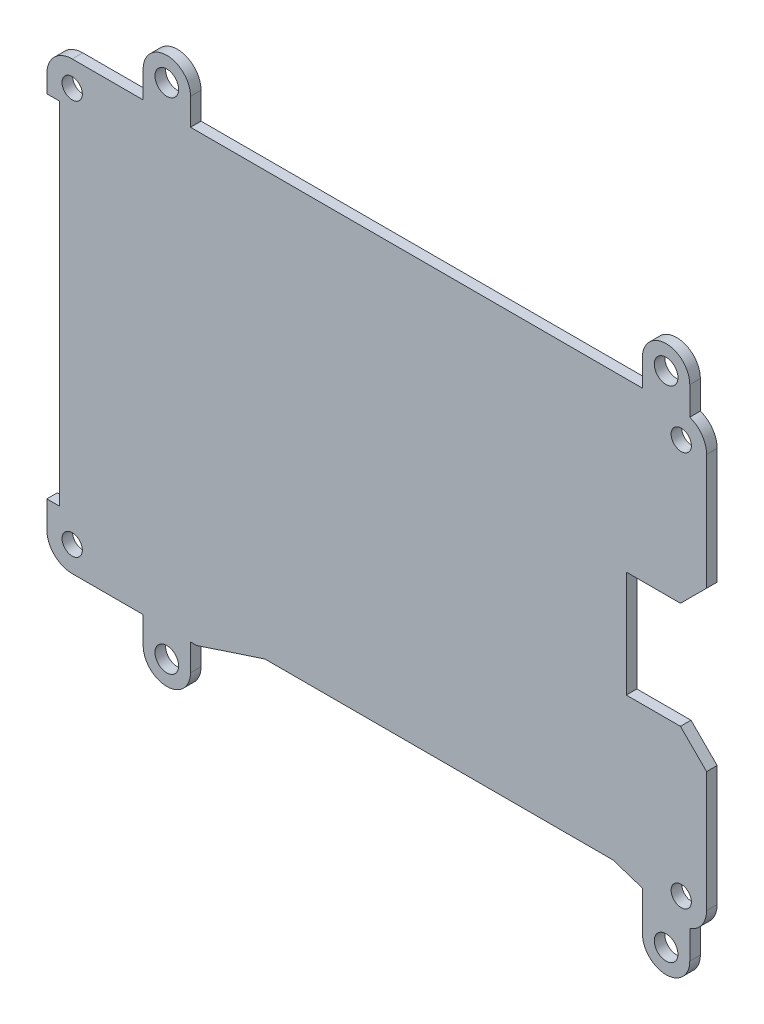
SolidWorks part; units mm, degrees
ref_plane "Front Plane" through (0, 0, 0) normal (0, 0, 1) x (1, 0, 0)
ref_plane "Top Plane" through (0, 0, 0) normal (0, 1, 0) x (1, 0, 0)
ref_plane "Right Plane" through (0, 0, 0) normal (1, 0, 0) x (0, 0, -1)
sketch "Sketch1" plane through (0, 0, 0) normal (0, 0, 1) x (1, 0, 0)
  line L0 (-301.9473, 111.7465) -> (-305.8779, 115.6771) construction
  line L1 (-305.8779, 115.6771) -> (-316.1078, 115.6771) construction
  line L2 (-316.1078, 115.6771) -> (-316.1078, 128.8851) construction
  line L3 (-316.1078, 128.8851) -> (-305.8779, 128.8851) construction
  line L4 (-305.8779, 128.8851) -> (-301.9473, 132.8157) construction
  line L5 (-301.9473, 132.8157) -> (-301.9473, 150.9704) construction
  line L6 (-305.7573, 154.7804) -> (-397.2471, 154.7804) construction
  line L7 (-401.0571, 150.9566) -> (-401.0571, 148.341) construction
  line L8 (-401.0571, 148.341) -> (-399.1521, 148.341) construction
  line L9 (-399.1521, 148.341) -> (-399.1521, 95.6449) construction
  line L10 (-399.1521, 95.6449) -> (-401.0571, 95.6449) construction
  line L11 (-401.0571, 95.6449) -> (-401.0571, 91.6593) construction
  line L12 (-397.2472, 87.8217) -> (-378.5565, 87.8217) construction
  line L13 (-378.5565, 87.8217) -> (-368.3165, 91.1883) construction
  line L14 (-368.3165, 91.1883) -> (-315.9973, 91.1883) construction
  line L15 (-315.9973, 91.1883) -> (-305.7573, 87.8217) construction
  line L16 (-301.9473, 91.6317) -> (-301.9473, 111.7465) construction
  line L17 (-301.9473, 111.7465) -> (-305.8779, 115.6771)
  line L18 (-305.8779, 115.6771) -> (-316.1078, 115.6771)
  line L19 (-316.1078, 115.6771) -> (-316.1078, 128.8851)
  line L20 (-316.1078, 128.8851) -> (-305.8779, 128.8851)
  line L21 (-305.8779, 128.8851) -> (-301.9473, 132.8157)
  line L22 (-301.9473, 132.8157) -> (-301.9473, 150.9704)
  line L23 (-305.7573, 154.7804) -> (-397.2471, 154.7804)
  line L24 (-401.0571, 150.9566) -> (-401.0571, 148.341)
  line L25 (-401.0571, 148.341) -> (-399.1521, 148.341)
  line L26 (-399.1521, 148.341) -> (-399.1521, 95.6449)
  line L27 (-399.1521, 95.6449) -> (-401.0571, 95.6449)
  line L28 (-401.0571, 95.6449) -> (-401.0571, 91.6593)
  line L29 (-397.2472, 87.8217) -> (-378.5565, 87.8217)
  line L30 (-378.5565, 87.8217) -> (-368.3165, 91.1883)
  line L31 (-368.3165, 91.1883) -> (-315.9973, 91.1883)
  line L32 (-315.9973, 91.1883) -> (-305.7573, 87.8217)
  line L33 (-301.9473, 91.6317) -> (-301.9473, 111.7465)
  circle A0 centre (-305.7573, 91.6317) radius 1.3559 construction
  circle A1 centre (-305.7573, 150.9704) radius 1.3559 construction
  circle A2 centre (-397.2471, 150.9704) radius 1.3559 construction
  circle A3 centre (-397.2472, 91.6317) radius 1.3559 construction
  circle A4 centre (-305.7573, 91.6317) radius 1.3559
  circle A5 centre (-305.7573, 150.9704) radius 1.3559
  circle A6 centre (-397.2471, 150.9704) radius 1.3559
  circle A7 centre (-397.2472, 91.6317) radius 1.3559
  arc A8 (-301.9473, 150.9704) -> (-305.7573, 154.7804) centre (-305.7573, 150.9704) ccw construction
  arc A9 (-397.2471, 154.7804) -> (-401.0571, 150.9566) centre (-397.2471, 150.9704) ccw construction
  arc A10 (-401.0571, 91.6593) -> (-397.2472, 87.8217) centre (-397.2472, 91.6317) ccw construction
  arc A11 (-305.7573, 87.8217) -> (-301.9473, 91.6317) centre (-305.7573, 91.6317) ccw construction
  arc A12 (-301.9473, 150.9704) -> (-305.7573, 154.7804) centre (-305.7573, 150.9704) ccw
  arc A13 (-397.2471, 154.7804) -> (-401.0571, 150.9566) centre (-397.2471, 150.9704) ccw
  arc A14 (-401.0571, 91.6593) -> (-397.2472, 87.8217) centre (-397.2472, 91.6317) ccw
  arc A15 (-305.7573, 87.8217) -> (-301.9473, 91.6317) centre (-305.7573, 91.6317) ccw
extrude "Boss-Extrude1" add sketch "Sketch1" along normal blind 1.5875
sketch "Sketch2" plane through (0, 0, 1.5875) normal (0, 0, 1) x (1, 0, 0)
  line L0 (-351.5022, 121.301) -> (-351.5022, 159.401) construction
  line L1 (-301.9473, 150.9704) -> (-301.9473, 91.6317) construction
  line L2 (-401.0571, 121.301) -> (-301.9473, 121.301) construction
  line L3 (-351.5022, 83.201) -> (-351.5022, 159.401) construction
  line L4 (-361.0272, 83.201) -> (-361.0272, 159.401)
  line L5 (-341.9772, 83.201) -> (-341.9772, 159.401)
  line L6 (-361.0272, 154.7804) -> (-341.9772, 154.7804)
  line L7 (-305.7573, 154.7804) -> (-397.2471, 154.7804) construction
  line L8 (-361.0272, 91.6317) -> (-341.9772, 91.6317)
  circle A0 centre (-351.5022, 159.401) radius 3.175
  arc A1 (-361.0272, 83.201) -> (-341.9772, 83.201) centre (-351.5022, 83.201) ccw
  arc A2 (-341.9772, 159.401) -> (-361.0272, 159.401) centre (-351.5022, 159.401) ccw
  circle A3 centre (-351.5022, 83.201) radius 3.175
  point P13 (-351.5022, 121.301)
  line M11 (-305.7573, 154.7804) -> (-397.2471, 154.7804)
  line M21 (-368.3165, 91.1883) -> (-315.9973, 91.1883)
  dimension "D1" = 6.35
  dimension "D2" = 38.1
  dimension "D3" = 19.05
extrude "Boss-Extrude2" [suppressed] add sketch "Sketch2" against normal blind 1.5875 contours L5 A2 L4 A0 M11 | L4 A1 L5 A3 M21
sketch "Sketch3" plane through (0, 0, 1.5875) normal (0, 0, 1) x (1, 0, 0)
  circle A0 centre (-397.2471, 150.9704) radius 1.524
  circle A1 centre (-305.7573, 150.9704) radius 1.524
  circle A2 centre (-305.7573, 91.6317) radius 1.524
  circle A3 centre (-397.2472, 91.6317) radius 1.524
  dimension "D1" = 3.048
extrude "Cut-Extrude1" cut sketch "Sketch3" against normal through all
sketch "Sketch4" plane through (0, 0, 1.5875) normal (0, 0, 1) x (1, 0, 0)
  line L0 (-301.9473, 133.571) -> (-305.8779, 129.6471)
  line L2 (-301.9473, 132.8157) -> (-301.9473, 150.9704) construction
  line L3 (-305.8779, 129.6471) -> (-314.0123, 129.6471)
  line L4 (-314.0123, 129.6471) -> (-314.0123, 113.6451)
  line L5 (-314.0123, 113.6451) -> (-305.8779, 113.6451)
  line L7 (-305.8779, 113.6451) -> (-301.9473, 109.7145)
  line L11 (-301.9473, 91.6317) -> (-301.9473, 111.7465) construction
  line L12 (-301.9473, 109.7145) -> (-301.9473, 133.571)
  dimension "D1" = 18.0828
  dimension "D2" = 16.002
  dimension "D3" = 8.1344
  dimension "D4" = 3.9306
  dimension "D5" = 23.8566
  dimension "D6" = 8.1344
  dimension "D7" = 5.5588
sketch "Sketch5" plane through (0, 0, 1.5875) normal (0, 0, 1) x (1, 0, 0)
  line L0 (-316.1078, 128.8851) -> (-305.8779, 128.8851) construction
  line L1 (-314.0123, 128.8851) -> (-316.1078, 128.8851)
  line L2 (-314.0123, 128.8851) -> (-314.0123, 115.6771)
  line L3 (-314.0123, 115.6771) -> (-316.1078, 115.6771)
  line L4 (-316.1078, 128.8851) -> (-316.1078, 115.6771)
  line L5 (-301.9473, 91.6317) -> (-301.9473, 111.7465) construction
  dimension "D1" = 12.065
extrude "Boss-Extrude3" add sketch "Sketch5" against normal up to vertex (1.5875 mm away) up to point (-316.1078, 128.8851, 0)
extrude "Cut-Extrude2" cut sketch "Sketch4" against normal through all
sketch "Sketch6" [suppressed] plane through (0, 0, 0) normal (0, 0, -1) x (-1, 0, 0)
  line L0 (351.5022, 154.7804) -> (351.5022, 91.1883) construction
  line L1 (368.3165, 91.1883) -> (315.9973, 91.1883) construction
  line L5 (305.7573, 154.7804) -> (397.2471, 154.7804) construction
  line L6 (379.7343, 158.5904) -> (379.7343, 154.7804)
  line L7 (379.7343, 154.7804) -> (386.7701, 154.7804)
  line L8 (386.7701, 154.7804) -> (386.7701, 158.5904)
  line L9 (347.9843, 87.3783) -> (347.9843, 91.1883)
  line L10 (347.9843, 91.1883) -> (355.0201, 91.1883)
  line L11 (355.0201, 91.1883) -> (355.0201, 87.3783)
  line L13 (316.2343, 154.7804) -> (316.2343, 158.5904)
  line L14 (323.2701, 154.7804) -> (316.2343, 154.7804)
  line L15 (323.2701, 158.5904) -> (323.2701, 154.7804)
  circle A0 centre (351.5022, 87.3783) radius 1.778
  circle A1 centre (351.5022, 87.3783) radius 3.5179
  circle A2 centre (383.2522, 158.5904) radius 3.5179
  circle A3 centre (383.2522, 158.5904) radius 1.778
  circle A4 centre (319.7522, 158.5904) radius 1.778
  circle A5 centre (319.7522, 158.5904) radius 3.5179
  dimension "D1" = 7.0358
  dimension "D2" = 7.0358
  dimension "D6" = 3.556
  dimension "D3" = 3.81
  dimension "D4" = 63.5
  dimension "D5" = 3.81
extrude "Boss-Extrude4" [suppressed] add sketch "Sketch6" against normal up to vertex up to point (-397.2472, 87.8217, 1.5875)
sketch "Sketch7" plane through (0, 0, 0) normal (0, 0, -1) x (-1, 0, 0)
  line L0 (397.2471, 154.7804) -> (397.2472, 87.8217) construction
  line L1 (308.0318, 158.801) -> (383.0318, 158.8011) construction
  line L2 (308.0318, 158.801) -> (308.0318, 83.801) construction
  line L3 (308.0318, 83.801) -> (383.0318, 83.801) construction
  line L4 (383.0318, 158.8011) -> (383.0318, 83.801) construction
  line L6 (397.2472, 121.301) -> (383.0318, 121.301) construction
  line L8 (304.4758, 158.801) -> (304.4758, 154.5584)
  line L9 (311.5878, 158.801) -> (311.5878, 154.7804)
  line L10 (305.7573, 154.7804) -> (397.2471, 154.7804) construction
  line L11 (379.4758, 158.8011) -> (379.4758, 154.7804)
  line L12 (386.5878, 158.8011) -> (386.5878, 154.7804)
  line L13 (386.5878, 154.7804) -> (379.4758, 154.7804)
  line L14 (379.4758, 83.801) -> (379.4758, 87.8217)
  line L15 (397.2472, 87.8217) -> (378.5565, 87.8217) construction
  line L16 (379.4758, 87.8217) -> (386.5878, 87.8217)
  line L17 (386.5878, 87.8217) -> (386.5878, 83.801)
  line L18 (304.4758, 83.801) -> (304.4758, 88.0437)
  line L19 (311.5878, 83.801) -> (311.5878, 89.7386)
  line L20 (315.9973, 91.1883) -> (305.7573, 87.8217) construction
  line L21 (301.9473, 133.571) -> (301.9473, 150.9704) construction
  circle A0 centre (308.0318, 158.801) radius 1.778
  circle A1 centre (383.0318, 158.8011) radius 1.778
  circle A2 centre (383.0318, 83.801) radius 1.778
  circle A3 centre (308.0318, 83.801) radius 1.778
  circle A4 centre (308.0318, 158.801) radius 3.556
  circle A5 centre (383.0318, 158.8011) radius 3.556
  circle A6 centre (308.0318, 83.801) radius 3.556
  circle A7 centre (383.0318, 83.801) radius 3.556
  arc A8 (305.7573, 154.7804) -> (301.9473, 150.9704) centre (305.7573, 150.9704) ccw construction
  arc A9 (301.9473, 91.6317) -> (305.7573, 87.8217) centre (305.7573, 91.6317) ccw construction
  arc M4 (301.9473, 91.6317) -> (305.7573, 87.8217) centre (305.7573, 91.6317) ccw
  line M5 (305.7573, 87.8217) -> (315.9973, 91.1883)
  line M8 (378.5565, 87.8217) -> (397.2472, 87.8217)
  line M16 (397.2471, 154.7804) -> (305.7573, 154.7804)
  arc M17 (305.7573, 154.7804) -> (301.9473, 150.9704) centre (305.7573, 150.9704) ccw
  dimension "D3" = 3.556
  dimension "D4" = 7.112
  dimension "D5" = 6.0845
  dimension "D1" = 75
  dimension "D2" = 75
extrude "Boss-Extrude5" add sketch "Sketch7" against normal blind 1.5875 contours A5 A1 | A5 L11 L12 M16 | A4 A0 | A4 L8 L9 M17 M16 | A6 L19 L18 M5 M4 | A6 A3 | A7 L17 L14 M8 | A7 A2 region at (-308.0318, 155.1622, 0) region at (-379.5575, 156.7907, 0) region at (-308.0318, 162.2565, 0) region at (-383.0318, 162.2565, 0) region at (-379.5575, 85.8114, 0) region at (-383.0318, 87.2565, 0) region at (-308.636, 87.5426, 0) region at (-308.0318, 87.2565, 0)
